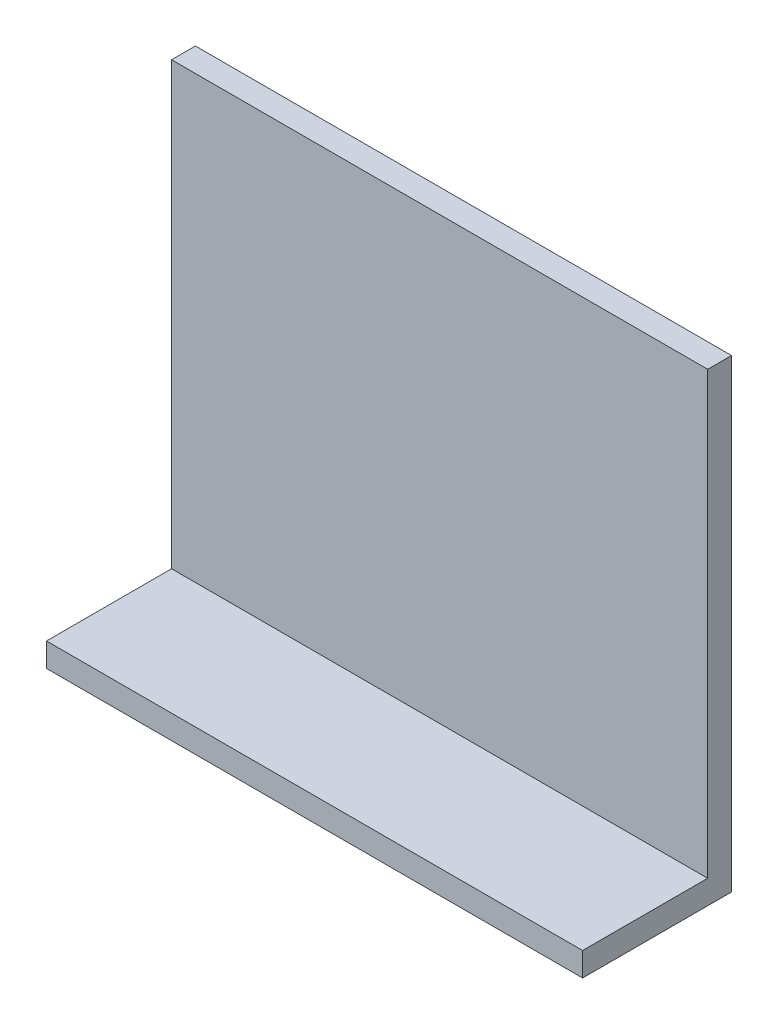
SolidWorks part; units mm, degrees
ref_plane "Front Plane" through (0, 0, 0) normal (0, 0, 1) x (1, 0, 0)
ref_plane "Top Plane" through (0, 0, 0) normal (0, 1, 0) x (1, 0, 0)
ref_plane "Right Plane" through (0, 0, 0) normal (1, 0, 0) x (0, 0, -1)
sketch "Sketch1" plane through (0, 0, 0) normal (0, 1, 0) x (1, 0, 0)
  line L1 (0, 0) -> (45, 0)
  line L2 (0, 0) -> (0, 12.5)
  line L3 (0, 12.5) -> (45, 12.5)
  line L4 (45, 0) -> (45, 12.5)
  dimension "D1" = 12.5
  dimension "D2" = 45
extrude "Boss-Extrude1" add sketch "Sketch1" along normal blind 2
sketch "Sketch2" plane through (0, 0, -12.5) normal (0, 0, -1) x (-1, 0, 0)
  line L1 (-45, 2) -> (0, 2)
  line L2 (-45, 2) -> (-45, 39)
  line L3 (-45, 39) -> (0, 39)
  line L4 (0, 2) -> (0, 39)
  dimension "D1" = 37
extrude "Boss-Extrude2" add sketch "Sketch2" against normal blind 2
